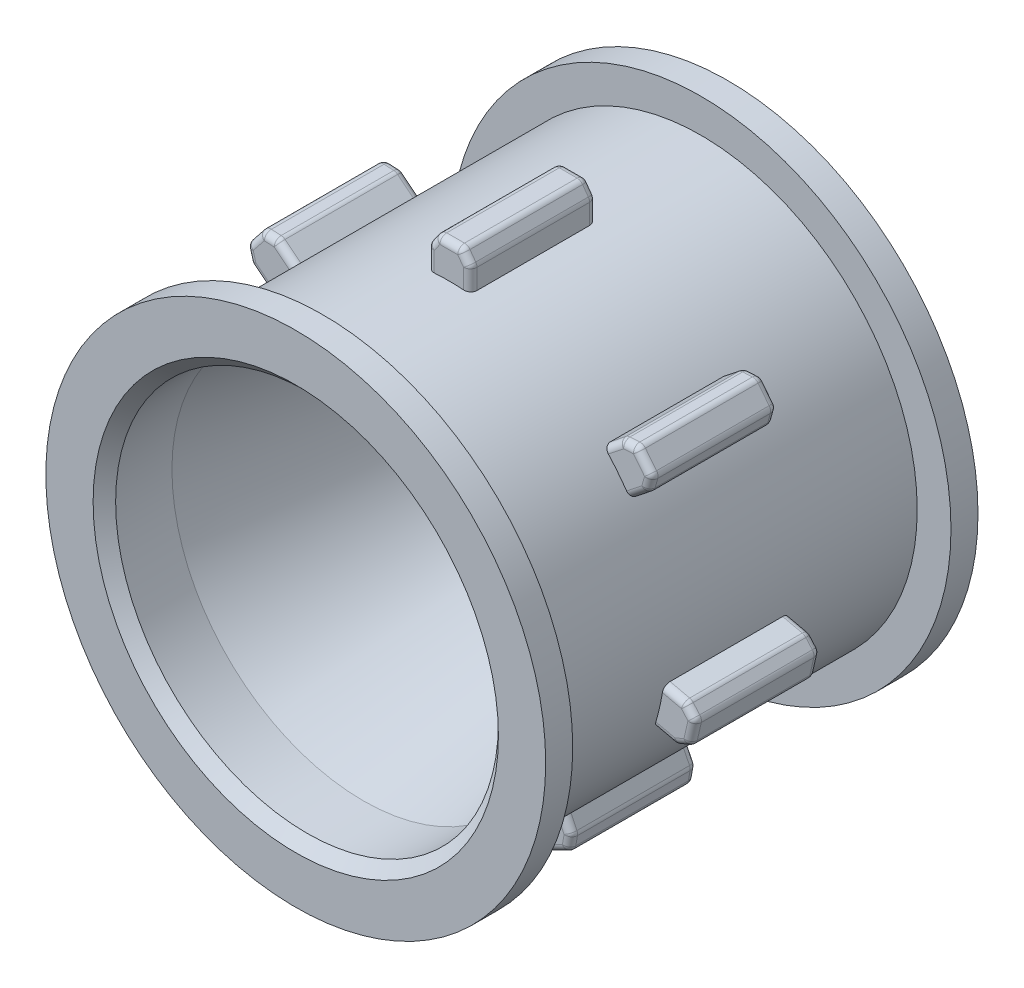
SolidWorks part; units mm, degrees
ref_plane "Ebene vorne" through (0, 0, 0) normal (0, 0, 1) x (1, 0, 0)
ref_plane "Ebene oben" through (0, 0, 0) normal (0, 1, 0) x (1, 0, 0)
ref_plane "Ebene rechts" through (0, 0, 0) normal (1, 0, 0) x (0, 0, -1)
sketch "Skizze1" plane through (0, 0, 0) normal (0, 0, 1) x (1, 0, 0)
  circle A0 centre (0, 0) radius 9.6
  dimension "D1" = 19.2
extrude "Laufrad" add sketch "Skizze1" along normal blind 8.4 and the other way blind 8.4
sketch "Skizze2" plane through (0, 0, 8.4) normal (0, 0, 1) x (1, 0, 0)
  circle A0 centre (0, 0) radius 11.1
  circle A1 centre (0, 0) radius 9.6 construction
  dimension "D1" = 1.5
extrude "Kettenführung" add sketch "Skizze2" along normal blind 1.2
mirror "Spiegeln Kettenführung" about plane through (0, 0, 0) normal (0, 0, 1) of "Kettenführung"
sketch "Skizze4" plane through (0, 0, -9.6) normal (0, 0, -1) x (-1, 0, 0)
  circle A0 centre (0, 0) radius 1
  dimension "D1" = 2
extrude "SchraubenBohrung M3" cut sketch "Skizze4" against normal through all
sketch "Skizze3" plane through (0, 0, -9.6) normal (0, 0, -1) x (-1, 0, 0)
  circle A0 centre (0, 0) radius 4.1
  dimension "D1" = 8.2
extrude "Kugellagersitz" cut sketch "Skizze3" against normal blind 2
sketch "Skizze5" plane through (0, 0, 0) normal (1, 0, 0) x (0, 0, -1)
  line L0 (-9.6, 0) -> (-9.6, 8.5)
  line L1 (-9.6, 8.5) -> (-6.6, 8.5)
  line L2 (-6.6, 8.5) -> (5.6, 6)
  line L3 (5.6, 6) -> (5.6, 0)
  line L4 (9.6, -4.1) -> (9.6, 4.1) construction
  line L5 (-9.6, 0) -> (7.6, 0) construction
  line L6 (-9.6, 0) -> (5.6, 0)
  line L7 (-9.6, 11.1) -> (-9.6, -11.1) construction
  dimension "D1" = 4
  dimension "D2" = 3
  dimension "D3" = 8.5
  dimension "D4" = 6
revolve "Schnitt-Rotation3" cut sketch "Skizze5" angle 360 about axis through (0, 0, -8.4) along (0, 0, 1)
chamfer "Fase1" distance 0.1 angle 45 1 edges at (-1, 0, -5.6) tangent propagation no
sketch "Skizze6" plane through (0, 0, 0) normal (0, 0, 1) x (1, 0, 0)
  line L0 (0, 0) -> (0, 10.3) construction
  line L1 (0, 10.3) -> (0, 11.1) construction
  line L2 (0.55, 11.1) -> (-0.55, 11.1)
  line L3 (-0.55, 11.1) -> (-0.95, 10.5424)
  line L4 (-0.95, 10.5424) -> (-0.95, 9.5529)
  line L5 (0.95, 10.5424) -> (0.95, 9.5529)
  line L6 (0.55, 11.1) -> (0.95, 10.5424)
  line L7 (-0.95, 9.5529) -> (0.95, 9.5529)
  circle A1 centre (0, 0) radius 9.6 construction
  dimension "D1" = 0.8
  dimension "D2" = 10.3
  dimension "D3" = 1.9
  dimension "D4" = 1.1
extrude "Zahn" add sketch "Skizze6" along normal blind 2.8 and the other way blind 2.8
fillet "Verrundung1" radius 0.3 14 edges at (0.95, 10.5424, 0) (-0.95, 10.5424, 0) (-0.95, 10.0476, -2.8) (-0.75, 10.8212, -2.8) (0, 11.1, -2.8) (0.75, 10.8212, -2.8) (0.95, 10.0476, -2.8) (-0.55, 11.1, 0) (0.55, 11.1, 0) (-0.95, 10.0476, 2.8) (-0.75, 10.8212, 2.8) (0, 11.1, 2.8) (0.75, 10.8212, 2.8) (0.95, 10.0476, 2.8)
pattern_circular "Kreismuster1" count 7 over 360 about axis through (0, 0, -8.4) along (0, 0, 1) of "Zahn", "Verrundung1"
sketch "Skizze8" plane through (0, 0, -9.6) normal (0, 0, -1) x (-1, 0, 0)
  line L0 (0, 11.1) -> (0, -11.1) construction
  line L1 (0, -11.1) -> (0, 11.1) construction
  line L2 (11.1, 0) -> (-11.1, 0) construction
  line L3 (2.1, 8.7) -> (2.1, -8.7)
  line L4 (2.1, -8.7) -> (-2.1, -8.7)
  line L5 (-2.1, -8.7) -> (-2.1, 8.7)
  line L6 (-2.1, 0) -> (2.1, 0)
  line L7 (2.1, 8.7) -> (-2.1, 8.7)
  circle A0 centre (0, 0) radius 11.1 construction
  point P12 (0, 0)
  dimension "D1" = 8.7
  dimension "D2" = 2.1
  dimension "D3" = 2.1
extrude "Auschnitt Antrieb Wage" cut sketch "Skizze8" against normal blind 2 contours L5 L6 L3 | L3 L7 L5 | L6 L5 L3 | L5 L4 L3 region at (0, 4.35, -9.6) region at (0, -4.35, -9.6)
sketch "Skizze10" plane through (0, 0, -9.6) normal (0, 0, -1) x (-1, 0, 0)
  line L0 (0, 11.1) -> (0, -11.1) construction
  line L1 (0, 10.56) -> (0, -10.56) construction
  line L2 (-8.5, 3.8) -> (8.5, 3.8)
  line L3 (8.5, 3.8) -> (8.5, -3.8)
  line L4 (8.5, -3.8) -> (-8.5, -3.8)
  line L5 (0, -3.8) -> (0, 3.8)
  line L6 (10.56, 0) -> (-10.56, 0) construction
  line L7 (-8.5, 3.8) -> (-8.5, -3.8)
  circle A0 centre (0, 0) radius 11.1 construction
  dimension "D1" = 8.5
  dimension "D2" = 3.8
  dimension "D3" = 3.8
extrude "Schnitt-Linear austragen2" cut sketch "Skizze10" against normal blind 2 contours L4 L3 L2 | L2 L7 L4 | L4 L5 L2 | L5 L4 L2 region at (4.25, 0, -9.6) region at (-4.25, 0, -9.6)
chamfer "Fase2" distance 0.5 angle 45 2 edges at (-6, 0, -5.6) (-8.5, 0, 9.6) first distance on face at (-1.1, 0, -5.6) first distance on face at (-8.5, 0, 9.6)
